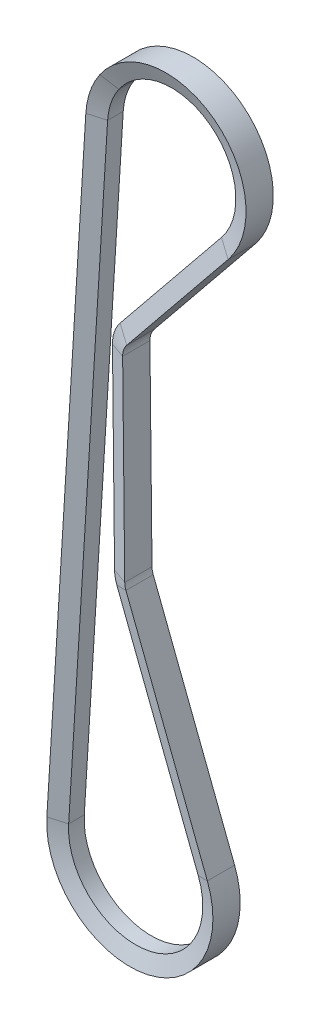
SolidWorks part; units mm, degrees
ref_plane "Front Plane" through (0, 0, 0) normal (0, 0, 1) x (1, 0, 0)
ref_plane "Top Plane" through (0, 0, 0) normal (0, 1, 0) x (1, 0, 0)
ref_plane "Right Plane" through (0, 0, 0) normal (1, 0, 0) x (0, 0, -1)
sketch "Sketch2" plane through (0, 0, 0) normal (0, 0, 1) x (1, 0, 0)
  line L0 (0, 0) -> (1, 0) construction
  line L1 (0, 0) -> (0, 1) construction
  line L3 (-41.5532, -217.8446) -> (-27.9464, 1.7318)
  line L4 (21.7402, -17.6455) -> (-13.6652, -61.2669)
  line L5 (-15.0845, -65.3366) -> (-14.3568, -133.3327)
  line L6 (-13.9311, -135.5516) -> (14.4949, -209.1867)
  arc A0 (-27.9464, 1.7318) -> (21.7402, -17.6455) centre (0, 0) cw
  arc A1 (14.4949, -209.1867) -> (-41.5532, -217.8446) centre (-12.5831, -219.6399) cw
  arc A2 (-13.6652, -61.2669) -> (-15.0845, -65.3366) centre (-8.7349, -65.2686) ccw
  arc A3 (-14.3568, -133.3327) -> (-13.9311, -135.5516) centre (-8.0072, -133.2647) ccw
ref_plane "Plane4" through (-23.0609, 15.8806, 0) normal (0.5672, 0.8236, 0) x (0.8236, -0.5672, 0)
sketch "Sketch3" plane through (-23.0609, 15.8806, 0) normal (0.5672, 0.8236, 0) x (0.8236, -0.5672, 0)
  line L0 (0, 4.7625) -> (0, -4.7625)
  line L1 (0, 4.7625) -> (5.588, 2.7286)
  line L2 (5.588, 2.7286) -> (5.588, -2.7286)
  line L3 (5.588, -2.7286) -> (0, -4.7625)
  line L4 (0, 0) -> (5.588, 0) construction
  point P2 (0, 0)
  dimension "D1" = 9.525
  dimension "D2" = 5.588
  dimension "D3" = 40
sweep "Sweep1" add profiles "Sketch3" path "Sketch2"
